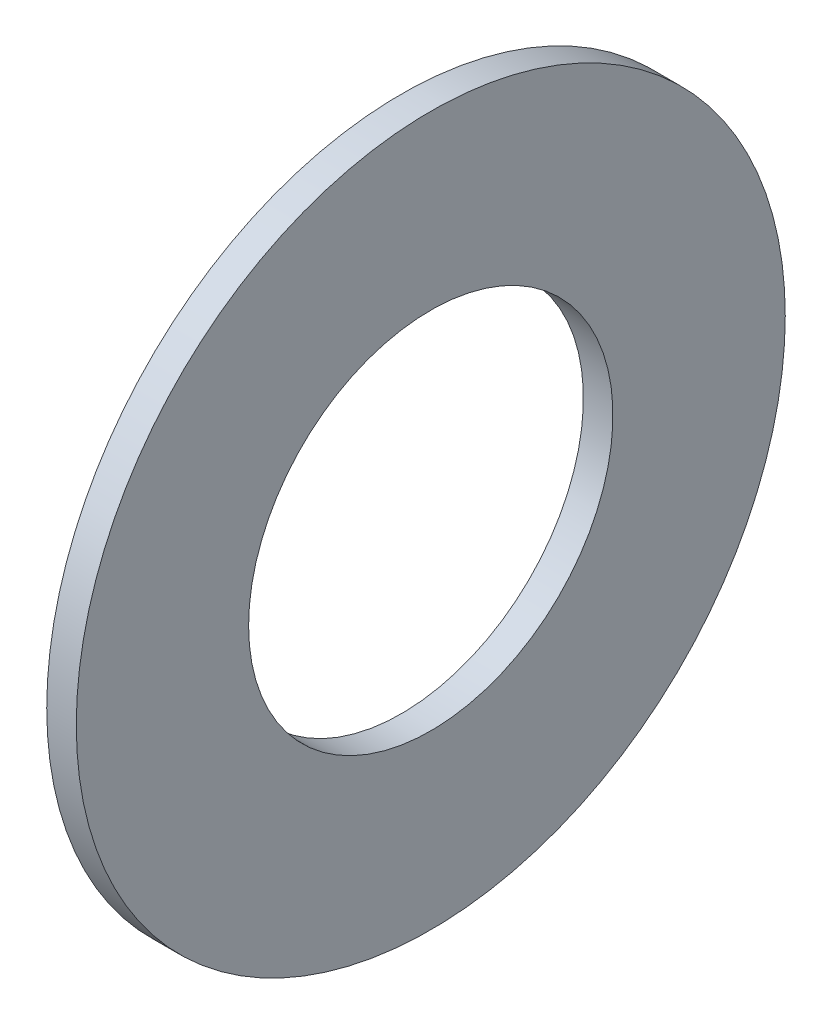
SolidWorks part; units mm, degrees
ref_plane "Plane1" through (0, 0, 0) normal (0, 0, 1) x (1, 0, 0)
ref_plane "Plane2" through (0, 0, 0) normal (0, 1, 0) x (1, 0, 0)
ref_plane "Plane3" through (0, 0, 0) normal (1, 0, 0) x (0, 0, -1)
sketch "Sketch1" plane through (0, 0, 0) normal (0, 0, 1) x (1, 0, 0)
  line L0 (-34.925, 0) -> (9.525, 0) construction
  line L1 (0, 18.5) -> (0, 36)
  line L2 (0, 36) -> (-3, 36)
  line L3 (-3, 36) -> (-3, 18.5)
  line L4 (-3, 18.5) -> (0, 18.5)
  dimension "Thickness" = 3
  dimension "Inside_dia" = 37
  dimension "Outside_dia" = 72
revolve "Base-Revolve" add sketch "Sketch1" angle 360 about L0
